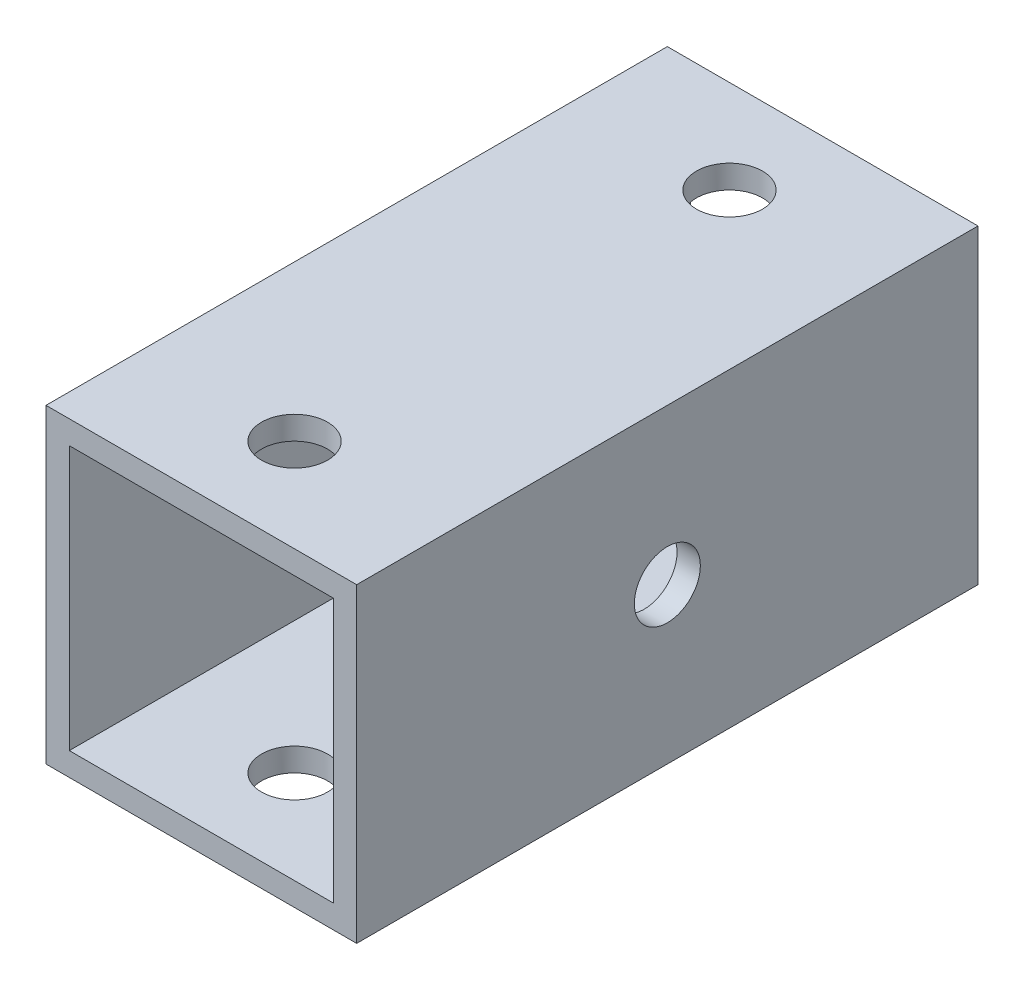
SolidWorks part; units mm, degrees
ref_plane "Front Plane" through (0, 0, 0) normal (0, 0, 1) x (1, 0, 0)
ref_plane "Top Plane" through (0, 0, 0) normal (0, 1, 0) x (1, 0, 0)
ref_plane "Right Plane" through (0, 0, 0) normal (1, 0, 0) x (0, 0, -1)
sketch "Sketch1" plane through (0, 0, 0) normal (0, 0, 1) x (1, 0, 0)
  line L0 (-8.5, -8.5) -> (8.5, -8.5)
  line L1 (-10, -10) -> (10, -10)
  line L2 (-10, -10) -> (-10, 10)
  line L3 (-10, 10) -> (10, 10)
  line L4 (10, -10) -> (10, 10)
  line L5 (-10, -10) -> (10, 10) construction
  line L6 (-10, 10) -> (10, -10) construction
  line L7 (8.5, -8.5) -> (8.5, 8.5)
  line L8 (-8.5, 8.5) -> (8.5, 8.5)
  line L9 (-8.5, -8.5) -> (-8.5, 8.5)
  point P0 (0, 0)
  dimension "D1" = 20
  dimension "D3" = 20
  dimension "D2" = 1.5
extrude "Boss-Extrude1" add sketch "Sketch1" against normal blind 40
sketch "Sketch2" plane through (0, 10, 0) normal (0, 1, 0) x (1, 0, 0)
  line L0 (10, 0) -> (-10, 0) construction
  line L1 (-10, 20) -> (10, 20) construction
  line L2 (-10, 40) -> (-10, 0) construction
  line L3 (10, 40) -> (10, 0) construction
  circle A0 centre (0, 6) radius 2.125
  circle A1 centre (0, 34) radius 2.125
  dimension "D1" = 4.25
  dimension "D2" = 6
extrude "Cut-Extrude1" cut sketch "Sketch2" against normal through all
sketch "Sketch3" plane through (10, 0, 0) normal (1, 0, 0) x (0, 0, -1)
  line L0 (20, 10) -> (20, -10) construction
  line L1 (40, 10) -> (0, 10) construction
  line L2 (40, -10) -> (0, -10) construction
  circle A0 centre (20, 0) radius 2.125
  dimension "D1" = 4.25
extrude "Cut-Extrude2" cut sketch "Sketch3" against normal through all
